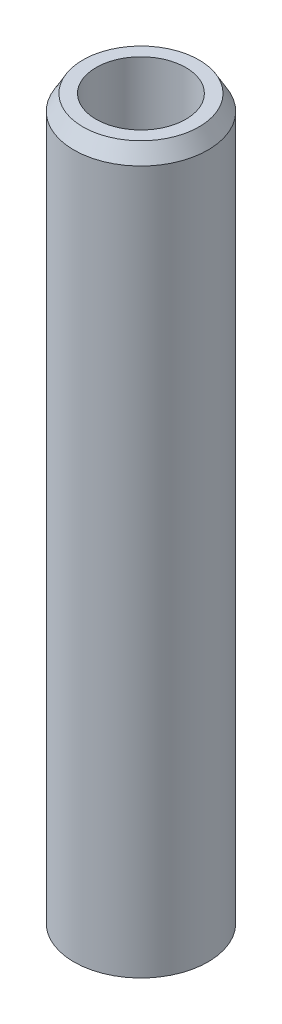
SolidWorks part; units mm, degrees
ref_plane "Front Plane" through (0, 0, 0) normal (0, 0, 1) x (1, 0, 0)
ref_plane "Top Plane" through (0, 0, 0) normal (0, 1, 0) x (1, 0, 0)
ref_plane "Right Plane" through (0, 0, 0) normal (1, 0, 0) x (0, 0, -1)
sketch "Sketch1" plane through (0, 0, 0) normal (0, 1, 0) x (1, 0, 0)
  circle A0 centre (0, 0) radius 10
  dimension "SHAFT_OD" = 20
extrude "Boss-Extrude1" add sketch "Sketch1" along normal blind 108.5655
sketch "Sketch2" plane through (0, 0, 0) normal (0, 1, 0) x (1, 0, 0)
  circle A0 centre (0, 0) radius 6.6958
  dimension "BORE_D" = 13.3916
extrude "Cut-Extrude1" cut sketch "Sketch2" along normal through all
chamfer "Chamfer1" distance 2.3194 angle 30 2 edges at (0, 108.5655, 10) (0, 0, 10) first distance on face at (0, 108.5655, 10) first distance on face at (0, 0, 6.6958)
